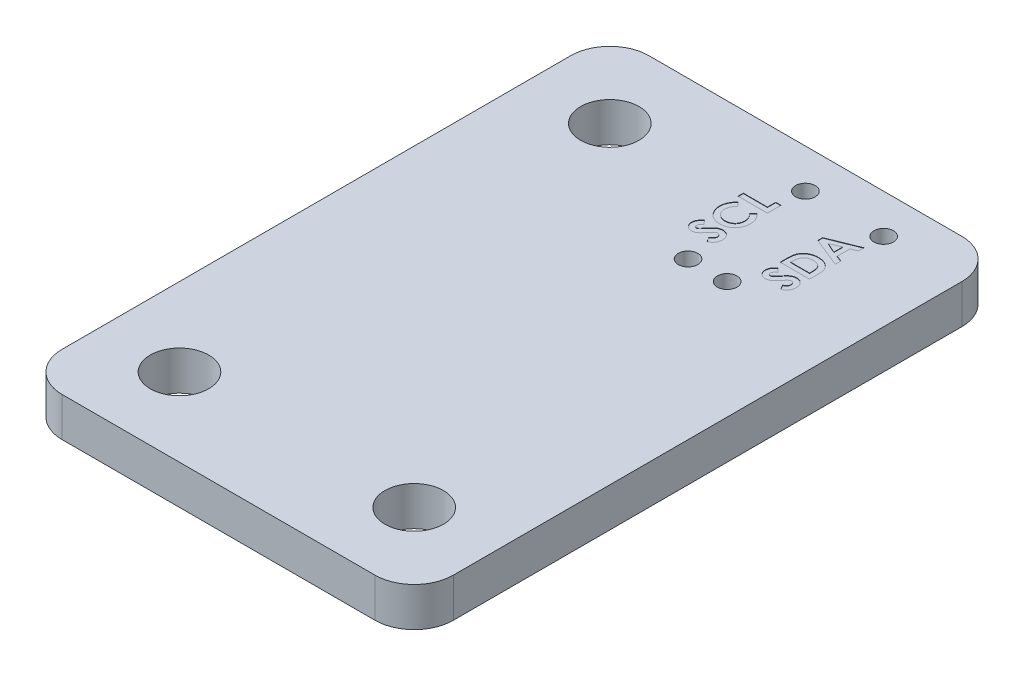
SolidWorks part; units mm, degrees
ref_plane "Front Plane" through (0, 0, 0) normal (0, 0, 1) x (1, 0, 0)
ref_plane "Top Plane" through (0, 0, 0) normal (0, 1, 0) x (1, 0, 0)
ref_plane "Right Plane" through (0, 0, 0) normal (1, 0, 0) x (0, 0, -1)
sketch "Sketch1" plane through (0, 0, 0) normal (0, 1, 0) x (1, 0, 0)
  line L1 (-12.7, -19.05) -> (12.7, -19.05)
  line L2 (-12.7, -19.05) -> (-12.7, 19.05)
  line L3 (-12.7, 19.05) -> (12.7, 19.05)
  line L4 (12.7, -19.05) -> (12.7, 19.05)
  line L5 (-12.7, -19.05) -> (12.7, 19.05) construction
  line L6 (-12.7, 19.05) -> (12.7, -19.05) construction
  point P0 (0, 0)
  dimension "D1" = 38.1
  dimension "D2" = 25.4
extrude "Boss-Extrude1" add sketch "Sketch1" along normal mid plane 2.54
fillet "Fillet1" radius 2.54 4 edges at (-12.7, 0, -19.05) (12.7, 0, -19.05) (-12.7, 0, 19.05) (12.7, 0, 19.05)
sketch "Sketch2" plane through (0, 1.27, 0) normal (0, 1, 0) x (1, 0, 0)
  line L0 (12.7, -16.51) -> (12.7, 16.51) construction
  line L1 (10.16, 19.05) -> (-10.16, 19.05) construction
  line L2 (2.54, 16.51) -> (2.54, 8.89) construction
  line L3 (7.62, 16.51) -> (7.62, 8.89) construction
  circle A0 centre (7.62, 16.51) radius 0.635
  circle A1 centre (2.54, 16.51) radius 0.635
  circle A2 centre (5.08, 8.89) radius 0.635
  circle A3 centre (2.54, 8.89) radius 0.635
  point P12 (0, 0)
  point P14 (0, 0)
  dimension "D6" = 1.27
  dimension "D1" = 5.08
  dimension "D2" = 5.08
  dimension "D3" = 2.54
  dimension "D4" = 2.54
  dimension "D5" = 7.62
  dimension "D7" = 7.62
  dimension "D8" = 10.16
extrude "Cut-Extrude1" cut sketch "Sketch2" against normal through all
sketch "Sketch4" plane through (0, 1.27, 0) normal (0, 1, 0) x (1, 0, 0)
  text T0 "<b>SCL</b>" font "Century Gothic" height 1.905
  text T1 "<b>SDA</b>" font "Century Gothic" height 1.905
extrude "Cut-Extrude2" cut sketch "Sketch4" against normal blind 0.0254
sketch "Sketch5" plane through (0, 1.27, 0) normal (0, 1, 0) x (1, 0, 0)
  line L1 (-12.7, 16.51) -> (-12.7, -16.51) construction
  line L2 (10.16, 19.05) -> (-10.16, 19.05) construction
  line L3 (-10.16, -19.05) -> (10.16, -19.05) construction
  line L4 (12.7, -16.51) -> (12.7, 16.51) construction
  circle A0 centre (-7.62, 13.97) radius 1.905
  circle A1 centre (-7.62, -13.97) radius 1.905
  circle A2 centre (7.62, -13.97) radius 1.905
  point P0 (-7.62, 13.97)
  point P2 (-7.62, -13.97)
  point P4 (7.62, -13.97)
  dimension "D1" = 3.81
  dimension "D2" = 5.08
  dimension "D3" = 5.08
  dimension "D4" = 5.08
  dimension "D5" = 5.08
  dimension "D6" = 5.08
hole_wizard "#6 Clearance Hole1" positions "Sketch5" profile "Sketch6" hole size "#6" standard "ANSI Inch" end condition through all
sketch "Sketch6" plane through (-7.62, 1.27, -13.97) normal (1, 0, 0) x (0, 0, 1)
  line L0 (0, 0) -> (0, 2.54)
  line L1 (0, 2.54) -> (1.8986, 2.54)
  line L2 (1.8986, 2.54) -> (1.8986, 0)
  line L5 (1.8986, 0) -> (0, 0)
  line L11 (0, -6.35) -> (0, 107.95) construction
  dimension "Thru Hole Dia." = 3.7973
  dimension "Thru Hole Depth" = 2.54
